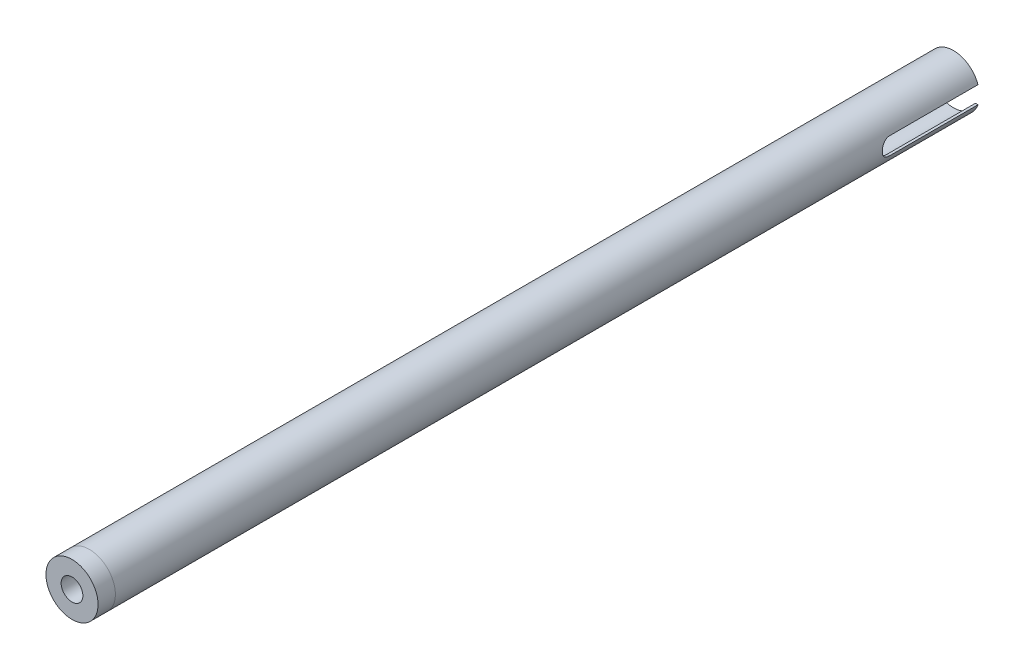
SolidWorks part; units mm, degrees
material "AISI 4130 Steel, normalized at 870C"
ref_plane "Front Plane" through (0, 0, 0) normal (0, 0, 1) x (1, 0, 0)
ref_plane "Top Plane" through (0, 0, 0) normal (0, 1, 0) x (1, 0, 0)
ref_plane "Right Plane" through (0, 0, 0) normal (1, 0, 0) x (0, 0, -1)
sketch "Axis" plane through (0, 0, 0) normal (0, 1, 0) x (1, 0, 0)
  line L0 (0, 0) -> (0, 322.3896) construction
  line L1 (0, 0) -> (0, -28.575) construction
  line L2 (0, 322.3896) -> (-9.525, 322.3896) construction
  line L3 (0, 356.4735) -> (-23.5893, 272.0626) construction
  dimension "D1" = 28.575
  dimension "D2" = 9.525
sketch "Sketch1" plane through (0, 0, 0) normal (0, 0, 1) x (1, 0, 0)
  line L0 (-9.525, 0) -> (9.525, 0) construction
  line L1 (-8.9803, 3.175) -> (8.9803, 3.175)
  line L2 (-8.9803, -3.175) -> (8.9803, -3.175)
  circle A0 centre (0, 0) radius 9.525
  circle A1 centre (0, 0) radius 8.636
  circle A2 centre (0, 0) radius 3.9688
  dimension "D1" = 19.05
  dimension "D3" = 7.9375
  dimension "D2" = 0.889
  dimension "D4" = 6.35
extrude "Threaded insert 1-1" add sketch "Sketch1" against normal blind 6.35 contours A2 L1 A1 | A1 L1 A0 | A2 L0 A1 L1 | A1 L0 A0 L1 | L0 A1 L2 A0 | L0 A2 L2 A1 | A2 L2 A1 | A1 L2 A0 | L0 A1 L2 A2 | L0 A0 L2 A1 | A0 L0 A1 L1 | A1 L0 A2 L1 region at (5.9465, 1.6355, 0) region at (5.9465, -1.6355, 0) region at (8.8881, 1.6046, 0) region at (8.8881, -1.6046, 0) region at (-5.9465, -1.6355, 0) region at (-5.9465, 1.6355, 0) region at (0, 5.5139, 0) region at (0, -5.5139, 0) region at (0, 8.8265, 0) region at (8.5057, -3.3655, 0) region at (-8.8881, -1.6046, 0) region at (-8.8881, 1.6046, 0)
extrude "Threaded insert 1-2" add sketch "Sketch1<3>" against normal blind 9.525 from surface contours A2 L1 A1 | A2 L0 A1 L1 | L0 A2 L2 A1 | A2 L2 A1 | L0 A1 L2 A2 | A1 L0 A2 L1 region at (5.9465, 1.6355, 0) region at (5.9465, -1.6355, 0) region at (-5.9465, -1.6355, 0) region at (-5.9465, 1.6355, 0) region at (0, 5.5139, 0) region at (0, -5.5139, 0) starting at face at (9.525, 0, -6.35)
sketch "Sketch1<3>" plane through (0, 0, 0) normal (0, 0, 1) x (1, 0, 0) same geometry as "Sketch1"
extrude "A-arm tube" add sketch "Sketch1<4>" against normal up to vertex (322.3896 mm away) from surface separate body contours A1 L1 A0 | A1 L0 A0 L1 | L0 A1 L2 A0 | A1 L2 A0 | L0 A0 L2 A1 | A0 L0 A1 L1 region at (8.8881, 1.6046, 0) region at (8.8881, -1.6046, 0) region at (0, 8.8265, 0) region at (8.5057, -3.3655, 0) region at (-8.8881, -1.6046, 0) region at (-8.8881, 1.6046, 0) up to point (0, 0, -322.3896) starting at face at (8.636, 0, -6.35)
sketch "Sketch1<4>" plane through (0, 0, 0) normal (0, 0, 1) x (1, 0, 0) same geometry as "Sketch1"
extrude "Apex slot" cut sketch "Sketch1<5>" along normal blind 35.56 from surface contours A0 L0 A1 L1 | L0 A0 L2 A1 | A1 L0 A0 L1 | L0 A1 L2 A0 region at (8.8881, 1.6046, 0) region at (8.8881, -1.6046, 0) region at (-8.8881, -1.6046, 0) region at (-8.8881, 1.6046, 0) starting at face at (8.636, 0, -322.3896)
sketch "Sketch1<5>" plane through (0, 0, 0) normal (0, 0, 1) x (1, 0, 0) same geometry as "Sketch1"
fillet "Fillet1" radius 3.175 4 edges at (-8.5057, 3.175, -286.8296) (-8.5057, -3.175, -286.8296) (8.5057, -3.175, -286.8296) (8.5057, 3.175, -286.8296)
equation "\"tube diameter\"= 3 / 4"
equation "\"tube thickness\"= .035"
equation "\"apex thickness\"= .25"
equation "\"tube slot\"= 1.4"
equation "\"D1@Sketch1\"=\"tube diameter\""
equation "\"D2@Sketch1\"=\"tube thickness\""
equation "\"threaded insert hole\"= .3125"
equation "\"D3@Sketch1\"=\"threaded insert hole\""
equation "\"D4@Sketch1\"=\"apex thickness\""
equation "\"D1@Apex slot\" = \"tube slot\""
equation "\"D1@Fillet1\"=\"apex thickness\"/2"
equation "\"D2@Axis\"=\"tube diameter\"/2"
